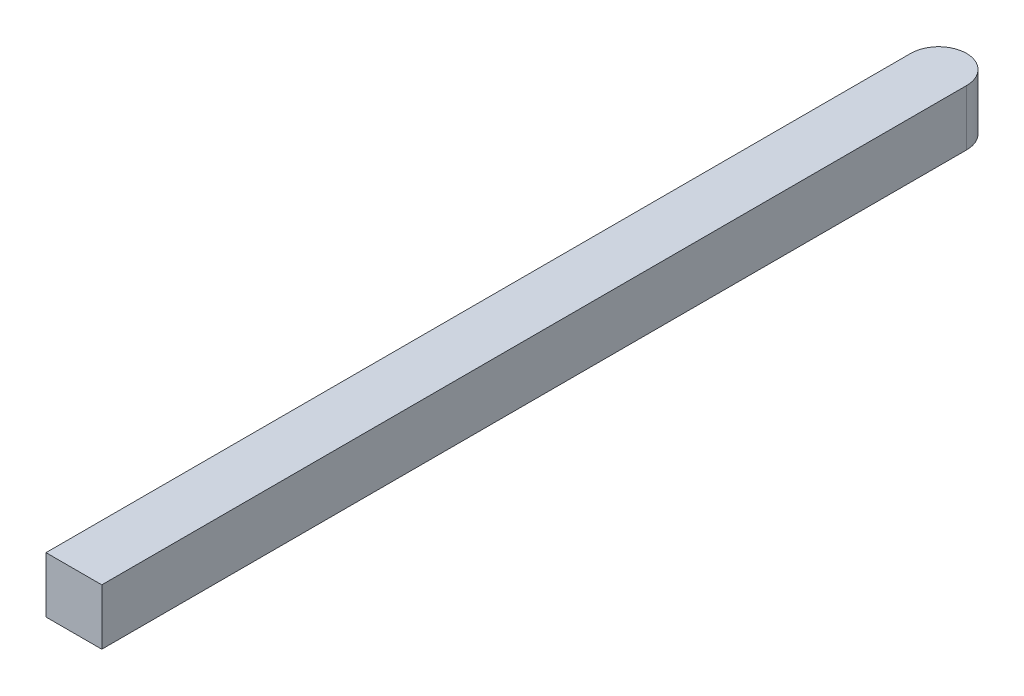
SolidWorks part; units mm, degrees
ref_plane "前视基准面" through (0, 0, 0) normal (0, 0, 1) x (1, 0, 0)
ref_plane "上视基准面" through (0, 0, 0) normal (0, 1, 0) x (1, 0, 0)
ref_plane "右视基准面" through (0, 0, 0) normal (1, 0, 0) x (0, 0, -1)
sketch "草图1" plane through (0, 0, 0) normal (0, 1, 0) x (1, 0, 0)
  line L1 (0, 0) -> (50, 0)
  line L2 (0, 0) -> (0, 800)
  line L3 (0, 800) -> (50, 800)
  line L4 (50, 0) -> (50, 800)
  dimension "D1" = 800
  dimension "D2" = 50
extrude "凸台-拉伸1" add sketch "草图1" along normal blind 50
fillet "圆角1" radius 25 2 edges at (0, 25, -800) (50, 25, -800)
